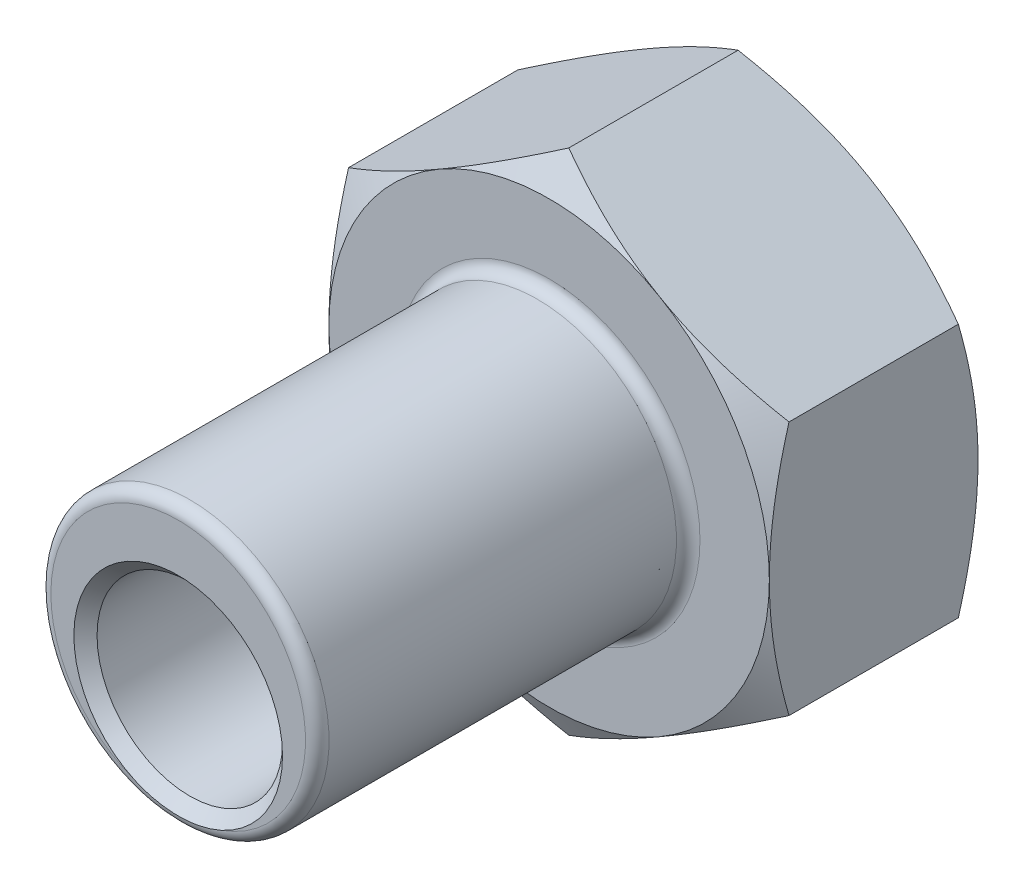
SolidWorks part; units mm, degrees
material "Plain Carbon Steel"
ref_plane "Front Plane" through (0, 0, 0) normal (0, 0, 1) x (1, 0, 0)
ref_plane "Top Plane" through (0, 0, 0) normal (0, 1, 0) x (1, 0, 0)
ref_plane "Right Plane" through (0, 0, 0) normal (1, 0, 0) x (0, 0, -1)
sketch "Sketch1" plane through (0, 0, 0) normal (1, 0, 0) x (0, 0, -1)
  line L0 (-12.5, 0) -> (12.5, 0) construction
  line L1 (-12.5, 6) -> (-12.5, -6) construction
  line L2 (12.5, 9.5) -> (12.5, -9.5) construction
  line L3 (-12.5, 6) -> (3.5, 6) construction
  line L4 (3.5, 6) -> (3.5, 9.5) construction
  line L5 (3.5, 9.5) -> (12.5, 9.5) construction
  line L6 (-12.5, -1.07) -> (0, -1.07) construction
  point P0 (-12.5, 2.93)
  point P4 (0, 0)
  point P8 (-12.5, 0)
  point P11 (12.5, 0)
  point P14 (-12.5, -5.07)
  point P15 (-12.5, -1.07)
sketch "Sketch2" plane through (0, 0, 0) normal (1, 0, 0) x (0, 0, -1)
  line L0 (-12.5, 0) -> (12.5, 0)
  line L1 (12.5, 0) -> (12.5, 9.5)
  line L2 (12.5, 9.5) -> (3.5, 9.5)
  line L3 (3.5, 9.5) -> (3.5, 6)
  line L4 (3.5, 6) -> (-12.5, 6)
  line L5 (-12.5, 6) -> (-12.5, 0)
revolve "Body Revolve" add sketch "Sketch2" angle 360 about L0
sketch "Sketch3" plane through (0, 0, -12.5) normal (0, 0, -1) x (-1, 0, 0)
  line L0 (0, 9.5) -> (0, -9.5) construction
  line L1 (0, 10.9697) -> (-9.5, 5.4848)
  line L2 (-9.5, 5.4848) -> (-9.5, -5.4848)
  line L3 (-9.5, -5.4848) -> (0, -10.9697)
  line L4 (0, -10.9697) -> (9.5, -5.4848)
  line L5 (9.5, -5.4848) -> (9.5, 5.4848)
  line L6 (9.5, 5.4848) -> (0, 10.9697)
  circle A0 centre (0, 0) radius 9.5 construction
  circle A1 centre (0, 0) radius 9.5 construction
extrude "Hex Extrude" add sketch "Sketch3" against normal up to vertex (9 mm away) up to point (0, 6, -3.5)
sketch "Sketch4" plane through (0, 0, -12.5) normal (0, 0, -1) x (-1, 0, 0)
  circle A0 centre (0, 0) radius 9.5 construction
  circle A1 centre (0, 0) radius 9.5
extrude "Hex Cut1" cut sketch "Sketch4" against normal through all draft 60 flip side to cut
sketch "Sketch5" plane through (0, 0, -3.5) normal (0, 0, 1) x (1, 0, 0)
  circle A1 centre (0, 0) radius 9.5
  circle A2 centre (0, 0) radius 9.5
  dimension "D1" = 0
extrude "Hex Cut2" cut sketch "Sketch5" against normal through all draft 60 flip side to cut
sketch "Sketch6" plane through (0, 0, 12.5) normal (0, 0, 1) x (1, 0, 0)
  circle A0 centre (0, -1.07) radius 4
extrude "Eccentric Hole Cut" cut sketch "Sketch6" against normal through all
fillet "Fillet" radius 0.508 2 edges at (6, 0, -3.5) (6, 0, 12.5)
chamfer "Chamfer" distance 0.5 angle 45 2 edges at (4, -1.07, -12.5) (4, -1.07, 12.5)
ref_axis "Center Axis 1" through (0, -1.07, -12) along (0, 0, 1)
ref_axis "Center Axis 2" through (0, 0, -2.992) along (0, 0, 1)
ref_plane "Contact Plane 1" through (0, 0, -3.5) normal (0, 0, 1) x (1, 0, 0)
equation "\"D1@Chamfer\" = \"ID@Sketch1\"/16"
